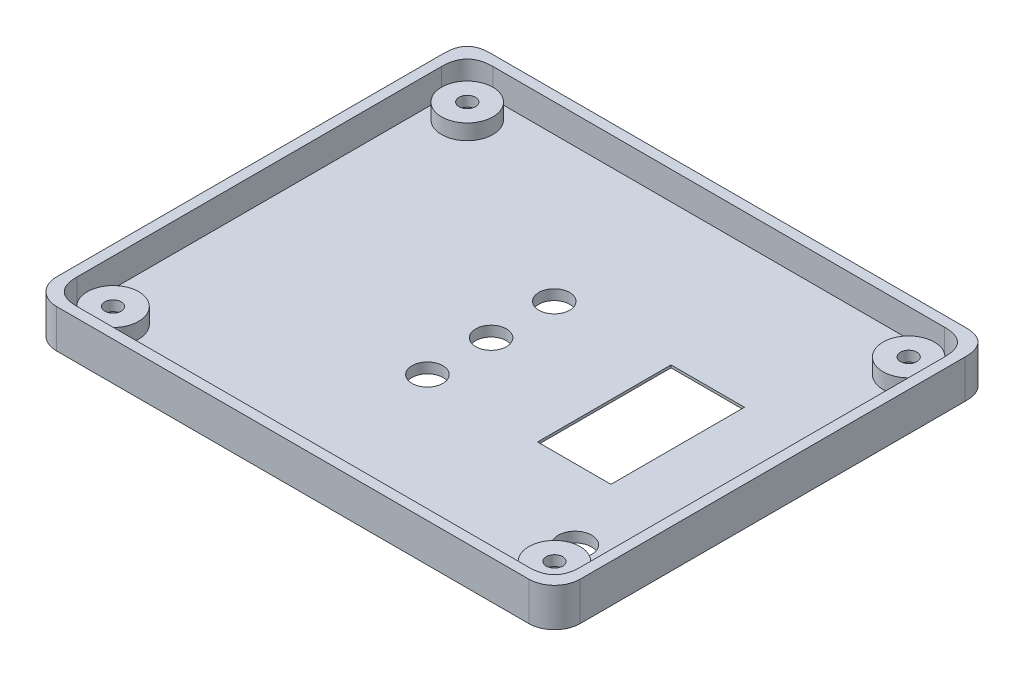
SolidWorks part; units mm, degrees
ref_plane "Front Plane" through (0, 0, 0) normal (0, 0, 1) x (1, 0, 0)
ref_plane "Top Plane" through (0, 0, 0) normal (0, 1, 0) x (1, 0, 0)
ref_plane "Right Plane" through (0, 0, 0) normal (1, 0, 0) x (0, 0, -1)
sketch "Sketch1" plane through (0, 0, 0) normal (0, 1, 0) x (1, 0, 0)
  line L0 (0, 0) -> (-82.5852, 0) construction
  line L1 (0, 0) -> (0, 51.3622) construction
  line L3 (51, 42.5) -> (-51, 42.5)
  line L4 (51, 42.5) -> (51, -42.5)
  line L5 (51, -42.5) -> (-51, -42.5)
  line L6 (-51, 42.5) -> (-51, -42.5)
  line L7 (51, 42.5) -> (-51, -42.5) construction
  line L8 (51, -42.5) -> (-51, 42.5) construction
  point P4 (0, 0)
  dimension "D1" = 102
  dimension "D2" = 85
extrude "Boss-Extrude1" add sketch "Sketch1" along normal blind 7.5
sketch "Sketch2" plane through (0, 7.5, 0) normal (0, 1, 0) x (1, 0, 0)
  line L5 (-49, 40.5) -> (49, 40.5)
  line L6 (-49, 40.5) -> (-49, -40.5)
  line L7 (-49, -40.5) -> (49, -40.5)
  line L8 (49, 40.5) -> (49, -40.5)
  line L9 (-49, 40.5) -> (49, -40.5) construction
  line L10 (-49, -40.5) -> (49, 40.5) construction
  point P0 (0, 0)
  dimension "D1" = 98
  dimension "D2" = 81
extrude "Cut-Extrude1" cut sketch "Sketch2" against normal blind 5.5
sketch "Sketch3" plane through (0, 0, 0) normal (0, -1, 0) x (-1, 0, 0)
  line L0 (51, -42.5) -> (-51, -42.5) construction
  line L1 (-51, -42.5) -> (-51, 42.5) construction
  line L3 (-51, 42.5) -> (51, 42.5) construction
  line L4 (51, 42.5) -> (51, -42.5) construction
  circle A0 centre (43, -34.5) radius 5
  circle A1 centre (-43, -34.5) radius 5
  circle A2 centre (43, 34.5) radius 5
  circle A3 centre (-43, 34.5) radius 5
  dimension "D5" = 8
  dimension "D9" = 10
  dimension "D10" = 10
  dimension "D11" = 10
  dimension "D12" = 10
  dimension "D1" = 8
  dimension "D2" = 8
  dimension "D3" = 8
  dimension "D4" = 8
  dimension "D6" = 8
  dimension "D7" = 8
  dimension "D8" = 8
extrude "Boss-Extrude2" add sketch "Sketch3" against normal blind 4 separate body contours A0
extrude "Boss-Extrude3" add sketch "Sketch3<3>" against normal blind 5
sketch "Sketch3<3>" plane through (0, 0, 0) normal (0, -1, 0) x (-1, 0, 0) same geometry as "Sketch3"
sketch "Sketch4" plane through (0, 0, 0) normal (0, -1, 0) x (1, 0, 0)
  circle A0 centre (-43, 34.5) radius 3
  circle A1 centre (43, 34.5) radius 3
  circle A2 centre (-43, -34.5) radius 3
  circle A3 centre (43, -34.5) radius 3
extrude "Cut-Extrude3" cut sketch "Sketch4" against normal blind 3
sketch "Sketch5" plane through (0, 0, 0) normal (0, -1, 0) x (1, 0, 0)
  circle A0 centre (-43, 34.5) radius 1.6
  circle A1 centre (43, 34.5) radius 1.6
  circle A2 centre (43, -34.5) radius 1.6
  circle A3 centre (-43, -34.5) radius 1.6
extrude "Cut-Extrude4" cut sketch "Sketch5" against normal blind 7.5
sketch "Sketch6" plane through (0, 0, 0) normal (0, -1, 0) x (1, 0, 0)
  line L0 (-51, 42.5) -> (51, 42.5) construction
  line L1 (18.2, 13) -> (32.5, 13)
  line L2 (18.2, 13) -> (18.2, -13)
  line L3 (18.2, -13) -> (32.5, -13)
  line L4 (32.5, 13) -> (32.5, -13)
  line L5 (51, 42.5) -> (51, -42.5) construction
  dimension "D1" = 29.5
  dimension "D2" = 18.5
  dimension "D3" = 14.3
  dimension "D4" = 26
extrude "Cut-Extrude5" cut sketch "Sketch6" against normal blind 10
chamfer "Chamfer1" distance 1.5 1 edges at (25.35, 0, 13)
chamfer "Chamfer2" distance 1.5 1 edges at (18.2, 0, 0.75)
chamfer "Chamfer3" distance 1.5 1 edges at (32.5, 0, 0.75)
chamfer "Chamfer4" distance 1.5 1 edges at (25.35, 0, -13)
sketch "Sketch7" plane through (0, 0, 0) normal (0, -1, 0) x (-1, 0, 0)
  line L0 (51, -42.5) -> (-51, -42.5) construction
  line L1 (-51, -42.5) -> (-51, 42.5) construction
  circle A0 centre (-39.2, -26.7) radius 3.25
  dimension "D1" = 15.8
  dimension "D2" = 11.8
extrude "Cut-Extrude6" cut sketch "Sketch7" against normal blind 10
fillet "Fillet2" radius 5 1 edges at (51, 3.75, 42.5)
fillet "Fillet3" radius 5 1 edges at (51, 3.75, -42.5) conic rho 0.5
fillet "Fillet4" radius 5 1 edges at (-51, 3.75, 42.5)
fillet "Fillet5" radius 5 1 edges at (-51, 3.75, -42.5) curvature continuous yes
fillet "Fillet6" radius 5 1 edges at (49, 4.75, -40.5) conic rho 0.5
fillet "Fillet7" radius 5 1 edges at (49, 4.75, 40.5) conic rho 0.5
fillet "Fillet8" radius 5 1 edges at (-49, 4.75, 40.5) conic rho 0.5
fillet "Fillet9" radius 5 1 edges at (-49, 4.75, -40.5) conic rho 0.5
sketch "Sketch8" plane through (0, 0, 0) normal (0, -1, 0) x (1, 0, 0)
  line L0 (46, -42.5) -> (-46, -42.5) construction
  line L1 (51, 37.5) -> (51, -37.5) construction
  circle A0 centre (-3.9, -12.35) radius 3
  circle A1 centre (-3.9, -0.05) radius 3
  circle A2 centre (-3.9, 12.35) radius 3
  dimension "D7" = 6
  dimension "D8" = 6
  dimension "D9" = 6
  dimension "D1" = 30.15
  dimension "D2" = 42.45
  dimension "D3" = 54.85
  dimension "D4" = 54.9
  dimension "D5" = 54.9
  dimension "D6" = 54.9
extrude "Cut-Extrude7" cut sketch "Sketch8" against normal blind 3
